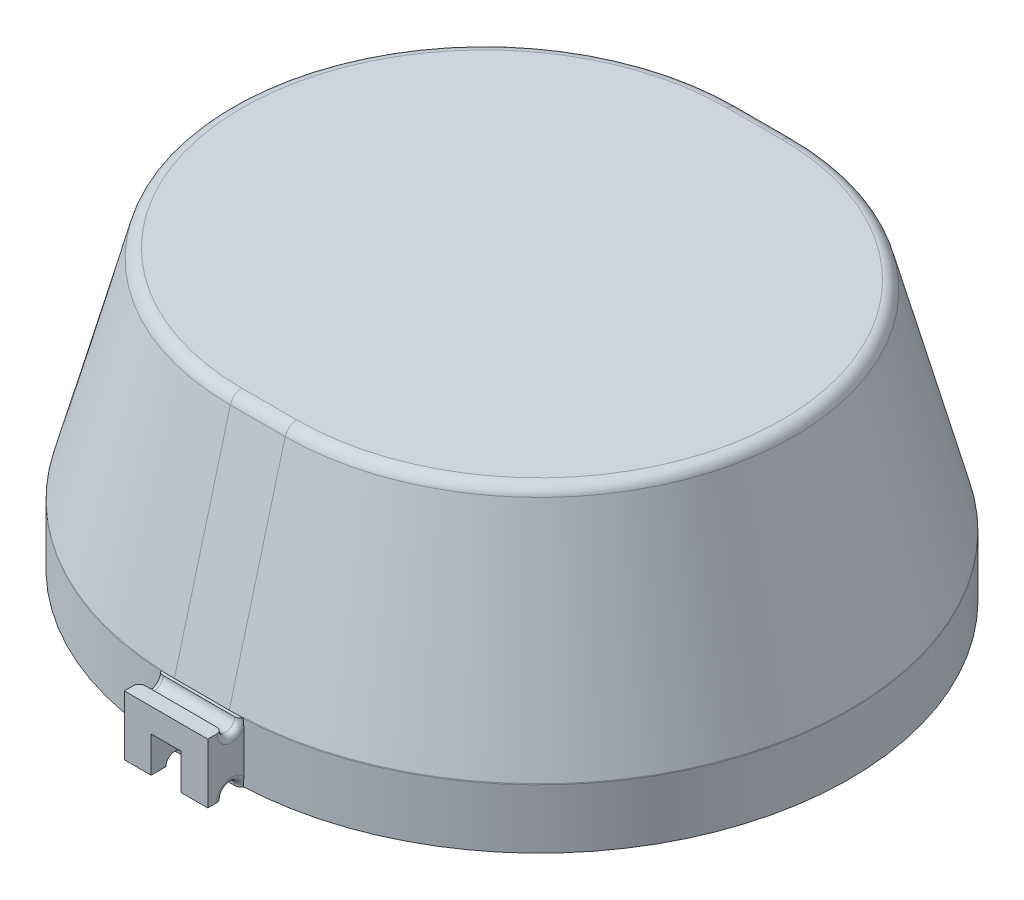
SolidWorks part; units mm, degrees
material "ABS"
ref_plane "Front Plane" through (0, 0, 0) normal (0, 0, 1) x (1, 0, 0)
ref_plane "Top Plane" through (0, 0, 0) normal (0, 1, 0) x (1, 0, 0)
ref_plane "Right Plane" through (0, 0, 0) normal (1, 0, 0) x (0, 0, -1)
ref_axis "Center" through (0, 21.7875, 0) along (0, -1, 0)
sketch "Sketch1" plane through (0, 0, 0) normal (0, 1, 0) x (1, 0, 0)
  line L0 (-2.3, 0) -> (2.3, 0) construction
  line L1 (-2.3, 25) -> (2.3, 25)
  line L2 (-2.3, -25) -> (2.3, -25)
  line L3 (-2.3, 0) -> (2.3, 0) construction
  line L4 (-2.3, 26) -> (2.3, 26)
  line L5 (-2.3, -26) -> (2.3, -26)
  arc A0 (-2.3, 25) -> (-2.3, -25) centre (-2.3, 0) ccw
  arc A1 (2.3, -25) -> (2.3, 25) centre (2.3, 0) ccw
  arc A2 (-2.3, 26) -> (-2.3, -26) centre (-2.3, 0) ccw
  arc A3 (2.3, -26) -> (2.3, 26) centre (2.3, 0) ccw
  point P2 (0, 0)
  point P9 (0, 0)
  dimension "D1" = 4.6
  dimension "D2" = 25
  dimension "D3" = 26
extrude "Boss-Extrude2" add sketch "Sketch1" along normal blind 5
sketch "Sketch2" plane through (0, 0, 0) normal (0, 1, 0) x (1, 0, 0)
  line L0 (-3.5, -25.9723) -> (-3.5, -27) construction
  line L1 (3.5, -25.9723) -> (3.5, -27) construction
  line L2 (-4.25, -25) -> (-4.25, -27)
  line L3 (4.25, -25) -> (4.25, -27)
  line L4 (-2.3, -25) -> (2.3, -25) construction
  line L5 (-4.25, -25) -> (4.25, -25)
  line L6 (0, -27) -> (0, -26) construction
  line L7 (-2.3, -26) -> (2.3, -26) construction
  line L8 (0, -27) -> (-3.5, -27) construction
  line L9 (0, -27) -> (3.5, -27) construction
  arc A0 (-3.5, -27) -> (3.5, -27) centre (0, -27) ccw construction
  arc A1 (-2.3, 26) -> (-2.3, -26) centre (-2.3, 0) ccw construction
  arc A3 (4.25, -27) -> (-4.25, -27) centre (0, -27) cw
  arc A4 (2.3, -26) -> (2.3, 26) centre (2.3, 0) ccw construction
  dimension "D1" = 2
  dimension "D2" = 0.75
  dimension "D3" = 0.75
  dimension "D4" = 3.5
ref_axis "F1" through (-2.3, 0, 0) along (0, 1, 0)
ref_axis "F2" through (2.3, 0, 0) along (0, 1, 0)
sketch "Sketch8" plane through (0, 0, 0) normal (1, 0, 0) x (0, 0, -1)
  line L1 (-25, 5) -> (-23.69, 5)
  line L2 (-25, 5) -> (-25, 3)
  line L3 (-25, 3) -> (-23.69, 3)
  line L4 (-23.69, 5) -> (-23.69, 3)
  dimension "D1" = 1.31
sweep "Sweep1" add profiles "Sketch8" path "Sketch1<2>"
sketch "Sketch1<2>" plane through (0, 0, 0) normal (0, 1, 0) x (1, 0, 0) same geometry as "Sketch1"
sketch "Sketch5" plane through (0, 0, 0) normal (-1, 0, 0) x (0, 0, 1)
  line L0 (-26, 5) -> (-21.1099, 23.25)
  line L1 (-21.1099, 23.25) -> (0, 23.25)
  line L2 (0, 23.25) -> (0, 22)
  line L3 (0, 22) -> (-20.1508, 22)
  line L4 (-20.1508, 22) -> (-24.7059, 5)
  line L7 (-24.7059, 5) -> (-26, 5)
  line L11 (-26, 5) -> (-26, 21.0394) construction
  line L12 (0, 21.7875) -> (0, -1.0375) construction
  dimension "D1" = 1.25
  dimension "D2" = 15
  dimension "D3" = 1.25
  dimension "D4" = 22
extrude "Boss-Extrude4" add sketch "Sketch5" along normal blind 2.3 and the other way blind 2.3
sketch "Sketch7" plane through (-2.3, 0, 0) normal (-1, 0, 0) x (0, 0, 1)
  line L0 (-26, 5) -> (-21.1099, 23.25)
  line L1 (-21.1099, 23.25) -> (0, 23.25)
  line L2 (0, 23.25) -> (0, 22)
  line L3 (0, 22) -> (-20.1508, 22)
  line L4 (-20.1508, 22) -> (-24.7059, 5)
  line L5 (-24.7059, 5) -> (-26, 5)
revolve "Revolve2" add sketch "Sketch7" angle 180 about axis through (-2.3, 0, 0) along (0, 1, 0)
mirror "Mirror1" about plane through (0, 0, 0) normal (0, 0, 1) of "Boss-Extrude4"
mirror "Mirror2" about plane through (0, 0, 0) normal (1, 0, 0) of "Revolve2"
sketch "Sketch11" plane through (0, 0, -25) normal (0, 0, -1) x (-1, 0, 0)
  line L0 (2.3, 5) -> (2.3, 0) construction
  line L1 (-2.3, 3) -> (2.3, 3)
  line L2 (-2.3, 3) -> (-2.3, 1.5)
  line L3 (-2.3, 1.5) -> (2.3, 1.5)
  line L4 (2.3, 3) -> (2.3, 1.5)
  line L5 (2.3, 3) -> (-2.3, 3) construction
  dimension "D1" = 1.5
extrude "Cut-Extrude5" cut sketch "Sketch11" along normal up to next (1 mm away) draft 5
fillet "Fillet8" radius 0.25 3 edges at (2.3, 2.25, -25) (0, 1.5, -25) (-2.3, 2.25, -25)
sketch "Sketch12" plane through (0, 3, 0) normal (0, -1, 0) x (1, 0, 0)
  line L0 (-3.5, 25) -> (-3.5, 29)
  line L1 (-3.5, 29) -> (3.5, 29)
  line L2 (3.5, 29) -> (3.5, 25)
  line L3 (3.5, 25) -> (-3.5, 25)
  line L4 (0, 25) -> (0, 23.69) construction
  line L5 (2.3, 25) -> (0, 25) construction
  point P2 (0, 25)
  dimension "D1" = 7
  dimension "D2" = 4
extrude "Boss-Extrude6" add sketch "Sketch12" along normal up to surface (3 mm away) and the other way up to vertex (2 mm away) up to face at (0, 0, 0) other way up to point (-2.3, 5, 26)
sketch "Sketch13" plane through (0, 0, 0) normal (0, -1, 0) x (1, 0, 0)
  line L0 (-2.3, 25) -> (2.3, 25) construction
  line L1 (1.25, 25) -> (-1.25, 25)
  line L2 (1.25, 25) -> (1.25, 29)
  line L3 (1.25, 29) -> (-1.25, 29)
  line L4 (-1.25, 25) -> (-1.25, 29)
  line L8 (0, 29) -> (0, 25) construction
  point P6 (0, 25)
  dimension "D1" = 2.5
  dimension "D2" = 4
extrude "Cut-Extrude6" cut sketch "Sketch13" against normal up to surface (3 mm away) up to face at (1.725, 3, 24.5087)
sketch "Sketch14" plane through (-3.5, 0, 0) normal (-1, 0, 0) x (0, 0, 1)
  line L0 (25.9723, 0) -> (29, 0) construction
  line L1 (29, 5) -> (25.9723, 5) construction
  line L2 (27.75, 5) -> (26.25, 5)
  line L3 (27.75, 0) -> (26.25, 0)
  line L4 (29, 0) -> (29, 5) construction
  arc A0 (26.25, 0) -> (27.75, 0) centre (27, 0) cw
  arc A1 (26.25, 5) -> (27.75, 5) centre (27, 5) ccw
  dimension "D1" = 0.75
  dimension "D2" = 0.75
  dimension "D3" = 2
extrude "Cut-Extrude7" cut sketch "Sketch14" against normal up to surface (7 mm away) up to face at (3.5, 2.5, 27.4861)
fillet "Fillet9" radius 0.5 4 edges at (3.5, 0.75, 27) (-3.5, 0.75, 27) (-3.5, 4.25, 27) (3.5, 4.25, 27)
fillet "Fillet10" radius 0.25 2 edges at (1.25, 1.5, 25) (-1.25, 1.5, 25)
fillet "Fillet6" radius 0.3 3 edges at (28.2937, 5, -0.5735) (0, 5, -26) (-28.2937, 5, -0.5735)
fillet "Fillet7" radius 1 8 edges at (0, 22, 20.1508) (22.4508, 22, 0) (0, 22, -20.1508) (0, 23.25, 21.1099) (23.4099, 23.25, 0) (0, 23.25, -21.1099) (-22.4508, 22, 0) (-23.4099, 23.25, 0)
